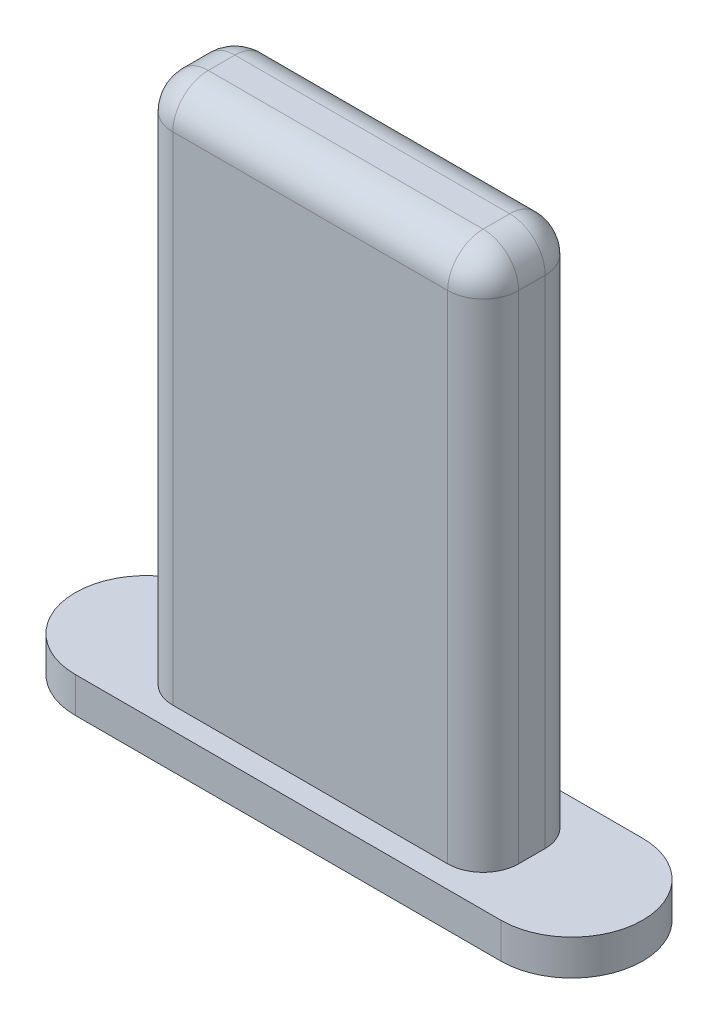
SolidWorks part; units mm, degrees
ref_plane "Front Plane" through (0, 0, 0) normal (0, 0, 1) x (1, 0, 0)
ref_plane "Top Plane" through (0, 0, 0) normal (0, 1, 0) x (1, 0, 0)
ref_plane "Right Plane" through (0, 0, 0) normal (1, 0, 0) x (0, 0, -1)
sketch "Sketch1" plane through (0, 0, 0) normal (0, 1, 0) x (1, 0, 0)
  line L0 (6, 0) -> (-6, 0) construction
  line L1 (6, -2) -> (-6, -2)
  line L2 (6, 2) -> (-6, 2)
  arc A0 (6, -2) -> (6, 2) centre (6, 0) ccw
  arc A1 (-6, 2) -> (-6, -2) centre (-6, 0) ccw
  point P2 (0, 0)
  dimension "D1" = 12
  dimension "D2" = 4
extrude "Boss-Extrude1" add sketch "Sketch1" along normal blind 1
sketch "Sketch2" plane through (0, 1, 0) normal (0, 1, 0) x (1, 0, 0)
  line L1 (4.875, -1.375) -> (-4.875, -1.375)
  line L2 (4.875, -1.375) -> (4.875, 1.375)
  line L3 (4.875, 1.375) -> (-4.875, 1.375)
  line L4 (-4.875, -1.375) -> (-4.875, 1.375)
  line L5 (4.875, -1.375) -> (-4.875, 1.375) construction
  line L6 (4.875, 1.375) -> (-4.875, -1.375) construction
  point P0 (0, 0)
  dimension "D1" = 9.75
  dimension "D2" = 2.75
extrude "Boss-Extrude2" add sketch "Sketch2" along normal blind 15
fillet "Fillet1" radius 1 4 edges at (0, 16, -1.375) (4.875, 16, 0) (0, 16, 1.375) (-4.875, 16, 0)
fillet "Fillet2" radius 1 8 edges at (4.5821, 15.7071, -1.0821) (-4.5821, 15.7071, -1.0821) (-4.5821, 15.7071, 1.0821) (4.5821, 15.7071, 1.0821) (4.875, 8, -1.375) (-4.875, 8, -1.375) (-4.875, 8, 1.375) (4.875, 8, 1.375)
sketch "Sketch3" plane through (0, 0, 0) normal (0, -1, 0) x (-1, 0, 0)
  circle A0 centre (0, 0) radius 1.5
  dimension "D1" = 3
